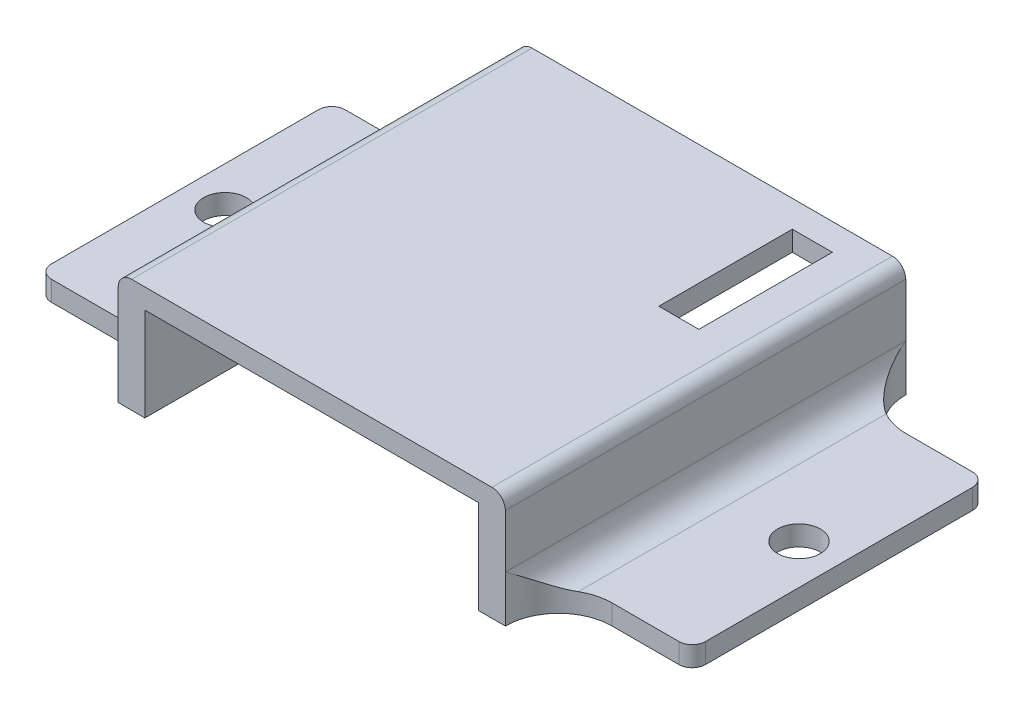
SolidWorks part; units mm, degrees
material "PEI"
ref_plane "Front Plane" through (0, 0, 0) normal (0, 0, 1) x (1, 0, 0)
ref_plane "Top Plane" through (0, 0, 0) normal (0, 1, 0) x (1, 0, 0)
ref_plane "Right Plane" through (0, 0, 0) normal (1, 0, 0) x (0, 0, -1)
sketch "Sketch1" plane through (0, 0, 0) normal (0, 0, 1) x (1, 0, 0)
  line L0 (0, 8.5) -> (0, -9.3416) construction
  line L1 (0, 0) -> (-24.5, 0)
  line L2 (-24.5, 0) -> (-24.5, 1.5)
  line L3 (-24.5, 1.5) -> (-14.5, 1.5)
  line L4 (-14.5, 1.5) -> (-14.5, 8.5)
  line L5 (-14.5, 8.5) -> (0, 8.5)
  line L6 (0, 8.5) -> (0, 7)
  line L7 (0, 7) -> (-12.5, 7)
  line L8 (-12.5, 7) -> (-12.5, 0)
  dimension "D1" = 2
  dimension "D2" = 1.5
  dimension "D3" = 12.5
  dimension "D4" = 24.5
  dimension "D5" = 1.5
  dimension "D6" = 7
extrude "Boss-Extrude1" add sketch "Sketch1" along normal mid plane 30 contours L8 L7 L6 L5 L4 L3 L2 L1 region at (-12.5948, 4.5086, 0)
mirror "Mirror1" about plane through (0, 0, 0) normal (1, 0, 0) of "Boss-Extrude1"
sketch "Sketch2" plane through (0, 8.5, 0) normal (0, 1, 0) x (1, 0, 0)
  line L0 (24.5, 15) -> (14.5, 15) construction
  line L1 (14.5, 15) -> (14.5, -15) construction
  line L2 (14.5, -15) -> (24.5, -15) construction
  line L3 (24.5, -15) -> (24.5, 15) construction
  line L4 (14.5, 15) -> (-14.5, 15)
  line L5 (-14.5, 15) -> (-14.5, -15)
  line L6 (-14.5, -15) -> (14.5, -15)
  line L7 (14.5, -15) -> (14.5, 15)
  line L8 (14.5, 15) -> (-14.5, 15)
  line L9 (-14.5, 15) -> (-14.5, -15)
  line L10 (-14.5, -15) -> (14.5, -15)
  line L11 (14.5, -15) -> (14.5, 15)
  line L12 (-14.5, 15) -> (-24.5, 15) construction
  line L13 (-24.5, 15) -> (-24.5, -15) construction
  line L14 (-24.5, -15) -> (-14.5, -15) construction
  line L15 (-14.5, -15) -> (-14.5, 15) construction
  line L16 (24.5, 15) -> (14.5, 15)
  line L17 (14.5, 15) -> (14.5, -15)
  line L18 (14.5, -15) -> (24.5, -15)
  line L19 (24.5, -15) -> (24.5, 15)
  line L20 (-14.5, 15) -> (-24.5, 15)
  line L21 (-24.5, 15) -> (-24.5, -15)
  line L22 (-24.5, -15) -> (-14.5, -15)
  line L23 (-14.5, -15) -> (-14.5, 15)
  line L24 (-14.5, 11) -> (-24.5, 11)
  line L25 (-14.5, -11) -> (-24.5, -11)
  line L26 (0, 0) -> (0, 15)
  line L27 (14.5, -11) -> (24.5, -11)
  line L28 (14.5, 11) -> (24.5, 11)
  line M10 (-14.5, 15) -> (-14.5, -15)
  line M12 (14.5, -15) -> (14.5, 15)
  dimension "D2" = 4
  dimension "D3" = 4
  dimension "D1" = 0
extrude "Cut-Extrude1" cut sketch "Sketch2" against normal through all contours L24 L20 L21 M10 | L25 L21 L22 M10 | L28 L19 L16 M12 | L27 L18 L19 M12 region at (19.5, 8.5, -13) region at (-19.5, 8.5, -13) region at (19.5, 8.5, 13) region at (-19.5, 8.5, 13)
sketch "Sketch4" plane through (0, 1.5, 0) normal (0, 1, 0) x (1, 0, 0)
  line L0 (24.5, 0) -> (21.5, 0)
  line L1 (0, 0) -> (0, -15.3594)
  line L4 (24.5, -11) -> (24.5, 11)
  line L5 (24.5, 11) -> (14.5, 11)
  line L6 (14.5, 11) -> (14.5, -11)
  line L7 (14.5, -11) -> (24.5, -11)
  line L8 (24.5, -11) -> (24.5, 11)
  line L9 (24.5, 11) -> (14.5, 11)
  line L10 (14.5, 11) -> (14.5, -11)
  line L11 (14.5, -11) -> (24.5, -11)
  circle A0 centre (21.5, 0) radius 1.6
  circle A1 centre (-21.5, 0) radius 1.6
  dimension "D3" = 3.2
  dimension "D2" = 3
  dimension "D1" = 0
extrude "Cut-Extrude2" cut sketch "Sketch4" against normal through all contours A0 | A1 region at (19.9453, 1.5, 0) region at (-21.5, 1.5, 0)
sketch "Sketch5" plane through (-12.5, 0, 0) normal (1, 0, 0) x (0, 0, -1)
  line L0 (-15, 0) -> (-10, 0)
  line L1 (-10, 0) -> (-10, 7)
  line L2 (-10, 7) -> (-2, 7)
  line L3 (-2, 7) -> (-2, 2)
  line L4 (15, 0) -> (15, 7)
  line L5 (15, 7) -> (-15, 7)
  line L6 (-15, 7) -> (-15, 0)
  line L7 (-15, 0) -> (15, 0)
  line L8 (15, 0) -> (15, 7)
  line L9 (15, 7) -> (-15, 7)
  line L10 (-15, 7) -> (-15, 0)
  line L11 (-15, 0) -> (15, 0)
  line L12 (-2, 2) -> (-10, 2)
  line L14 (12, 2) -> (9, 2)
  line L15 (12, 2) -> (12, 7)
  line L16 (12, 7) -> (9, 7)
  line L17 (9, 2) -> (9, 7)
  line M10 (15, 7) -> (-15, 7)
  dimension "D2" = 2
  dimension "D3" = 5
  dimension "D4" = 8
  dimension "D5" = 3
  dimension "D6" = 5
  dimension "D7" = 3
  dimension "D1" = 0
extrude "Cut-Extrude3" cut sketch "Sketch5" against normal through all contours L12 L3 L1 M10 | L17 L14 L15 L9 region at (-12.5, 4.5, 6) region at (-12.5, 4.5, -10.5)
sketch "Sketch7" plane through (0, 8.5, 0) normal (0, 1, 0) x (1, 0, 0)
  line L1 (14.5, 15) -> (8, 15)
  line L2 (14.5, 15) -> (14.5, 3)
  line L3 (14.5, 3) -> (8, 3)
  line L4 (14.5, 15) -> (-14.5, 15)
  line L5 (-14.5, 15) -> (-14.5, -15)
  line L6 (-14.5, -15) -> (14.5, -15)
  line L7 (14.5, -15) -> (14.5, 15)
  line L8 (14.5, 15) -> (-14.5, 15)
  line L9 (-14.5, 15) -> (-14.5, -15)
  line L10 (-14.5, -15) -> (14.5, -15)
  line L11 (14.5, -15) -> (14.5, 15)
  line L12 (8, 15) -> (8, 3)
  line L13 (8, 3) -> (11, 3)
  line L14 (8, 3) -> (8, 13)
  line L15 (8, 13) -> (11, 13)
  line L16 (11, 3) -> (11, 13)
  dimension "D2" = 6.5
  dimension "D3" = 12
  dimension "D4" = 2
  dimension "D5" = 3.5
  dimension "D1" = 0
extrude "Cut-Extrude4" cut sketch "Sketch7" against normal up to surface (1.5 mm away) contours L3 L16 L15 L12 region at (9.5, 8.5, -8) up to face at (-9, 7, -1.5)
fillet "Fillet1" radius 2 1 edges at (14.5, 1.5, 0)
fillet "Fillet2" radius 4 4 edges at (14.5, 1.75, -11) (14.5, 1.75, 11) (-14.5, 0.75, 11) (-14.5, 0.75, -11)
fillet "Fillet3" radius 1 6 edges at (-14.5, 8.5, 0) (14.5, 8.5, 0) (24.5, 0.75, -11) (24.5, 0.75, 11) (-24.5, 0.75, 11) (-24.5, 0.75, -11)
fillet "Fillet4" radius 1 8 edges at (-13.5, 7, 2) (-13.5, 7, 10) (-13.5, 7, -12) (-13.5, 7, -9) (-13.5, 2, 10) (-13.5, 2, 2) (-13.5, 2, -12) (-13.5, 2, -9)
fillet "Fillet5" radius 2 1 edges at (-14.5, 1.5, 0)
